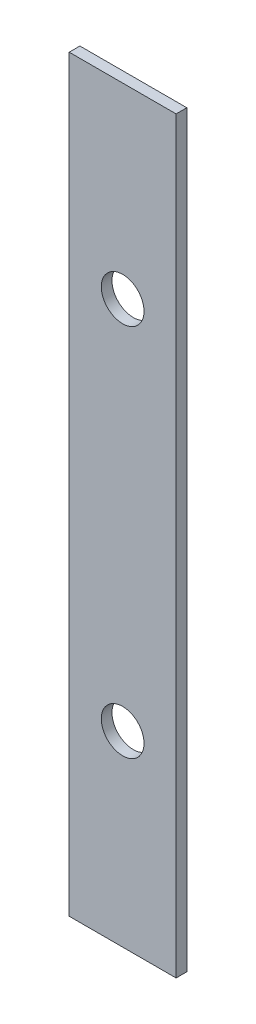
SolidWorks part; units mm, degrees
ref_plane "Front Plane" through (0, 0, 0) normal (0, 0, 1) x (1, 0, 0)
ref_plane "Top Plane" through (0, 0, 0) normal (0, 1, 0) x (1, 0, 0)
ref_plane "Right Plane" through (0, 0, 0) normal (1, 0, 0) x (0, 0, -1)
sketch "Sketch1" plane through (0, 0, 0) normal (0, 0, 1) x (1, 0, 0)
  line L0 (0, 0) -> (20, 0) construction
  line L1 (-20, 140) -> (20, 140)
  line L2 (-20, 140) -> (-20, -140)
  line L3 (-20, -140) -> (20, -140)
  line L4 (20, 140) -> (20, -140)
  line L5 (-20, 140) -> (20, -140) construction
  line L6 (-20, -140) -> (20, 140) construction
  point P0 (0, 0)
  dimension "D1" = 280
  dimension "D2" = 40
extrude "Boss-Extrude1" add sketch "Sketch1" along normal blind 4 contours L1 L4 L3 L2
ref_plane "Plane1" through (0, 0, 0) normal (0, 0, -1) x (-1, 0, 0)
sketch "Sketch3" plane through (0, 0, 0) normal (0, 0, -1) x (-1, 0, 0)
  line L0 (20, 70) -> (-20, 70) construction
  line L1 (-20, -70) -> (20, -70) construction
  circle A0 centre (0, 70) radius 8
  circle A1 centre (0, -70) radius 8
extrude "Boss-Extrude2" add sketch "Sketch3" against normal blind 4
extrude "Cut-Extrude1" cut sketch "Sketch3<2>" against normal blind 4
sketch "Sketch3<2>" plane through (0, 0, 0) normal (0, 0, -1) x (-1, 0, 0) same geometry as "Sketch3"
